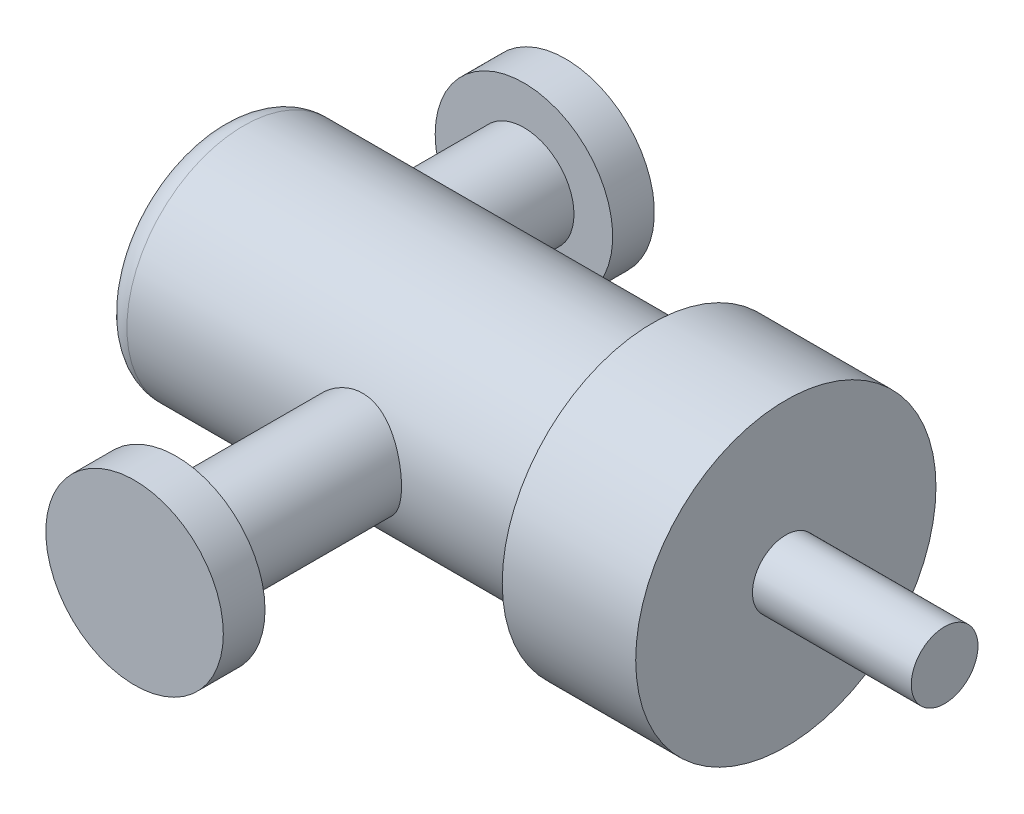
SolidWorks part; units mm, degrees
ref_plane "Front" through (0, 0, 0) normal (0, 0, 1) x (1, 0, 0)
ref_plane "Top" through (0, 0, 0) normal (0, 1, 0) x (1, 0, 0)
ref_plane "Right" through (0, 0, 0) normal (1, 0, 0) x (0, 0, -1)
sketch "Sketch1" plane through (0, 0, 0) normal (1, 0, 0) x (0, 0, -1)
  circle A0 centre (0, 0) radius 22.225
  dimension "D1" = 44.45
extrude "Extrude1" add sketch "Sketch1" along normal blind 82.55
sketch "Sketch2" plane through (0, 0, 0) normal (0, 0, 1) x (1, 0, 0)
  circle A0 centre (47.498, 0) radius 9.525
  dimension "D1" = 19.05
  dimension "D2" = 47.498
extrude "Extrude2" add sketch "Sketch2" along normal blind 63.5
sketch "Sketch3" plane through (0, 0, 0) normal (0, 0, 1) x (1, 0, 0)
  circle A0 centre (19.05, 0) radius 9.525
  dimension "D2" = 19.05
  dimension "D1" = 28.448
extrude "Extrude3" add sketch "Sketch3" against normal blind 46.99
sketch "Sketch4" plane through (0, 0, -46.99) normal (0, 0, -1) x (-1, 0, 0)
  circle A0 centre (-19.05, 0) radius 16.891
  dimension "D1" = 33.782
extrude "Extrude4" add sketch "Sketch4" against normal blind 7.9375
sketch "Sketch5" plane through (0, 0, 63.5) normal (0, 0, 1) x (1, 0, 0)
  circle A0 centre (47.498, 0) radius 16.891
  dimension "D1" = 33.782
extrude "Extrude5" add sketch "Sketch5" against normal blind 7.9375
sketch "Sketch6" plane through (82.55, 0, 0) normal (1, 0, 0) x (0, 0, -1)
  circle A0 centre (0, 0) radius 28.575
  dimension "D1" = 57.15
extrude "Extrude6" add sketch "Sketch6" along normal blind 25.4
sketch "Sketch7" plane through (107.95, 0, 0) normal (1, 0, 0) x (0, 0, -1)
  circle A0 centre (0, 0) radius 6.35
  dimension "D1" = 12.7
extrude "Extrude7" add sketch "Sketch7" along normal blind 30.226
sketch "Sketch8" plane through (0, 0, 63.5) normal (0, 0, 1) x (1, 0, 0)
  point P0 (47.498, 0)
ref_axis "Valve axis" through (138.176, 0, 0) along (-1, 0, 0)
fillet "Fillet1" radius 4.7625 1 edges at (0, 0, -22.225)
